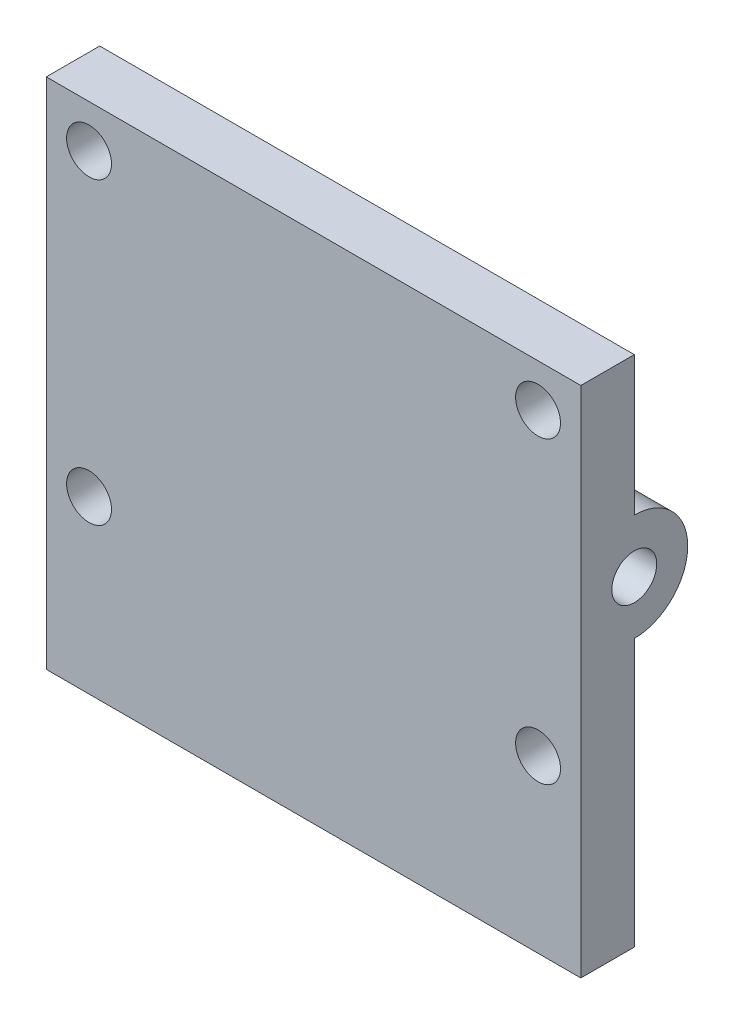
SolidWorks part; units mm, degrees
ref_plane "Płaszczyzna przednia" through (0, 0, 0) normal (0, 0, 1) x (1, 0, 0)
ref_plane "Płaszczyzna górna" through (0, 0, 0) normal (0, 1, 0) x (1, 0, 0)
ref_plane "Płaszczyzna prawa" through (0, 0, 0) normal (1, 0, 0) x (0, 0, -1)
sketch "Szkic2" plane through (0, 0, 0) normal (0, 0, 1) x (1, 0, 0)
  line L1 (-0.1189, 0.1751) -> (-0.1189, 24.1751)
  line L5 (24.8811, 24.1751) -> (24.8811, 0.1751)
  line L6 (-0.1189, 24.1751) -> (24.8811, 24.1751)
  line L17 (24.8811, 0.1751) -> (-0.1189, 0.1751)
  circle A0 centre (22.8811, 22.1751) radius 1.05
  circle A1 centre (22.8811, 8.1751) radius 1.05
  circle A2 centre (1.8811, 22.1751) radius 1.05
  circle A3 centre (1.8811, 8.1751) radius 1.05
  dimension "D1" = 2.1
  dimension "D2" = 2
  dimension "D3" = 2
  dimension "D4" = 14
  dimension "D5" = 21
  dimension "D7" = 25
  dimension "D8" = 24
extrude "Dodanie-wyciągnięcie1" add sketch "Szkic2" along normal blind 5
sketch "Szkic3" plane through (24.8811, 0, 0) normal (1, 0, 0) x (0, 0, -1)
  line L0 (0, 0.1751) -> (0, 24.1751) construction
  line L2 (-5, 24.1751) -> (0, 24.1751) construction
  circle A0 centre (-2.5, 15.1751) radius 1.05
  dimension "D1" = 2.1
  dimension "D3" = 9
  dimension "D2" = 2.5
extrude "Wytnij-wyciągnięcie1" cut sketch "Szkic3" against normal through all
sketch "Szkic4" plane through (-0.1189, 0, 0) normal (-1, 0, 0) x (0, 0, 1)
  line L0 (2.5, 24.1751) -> (2.5, 17.6751)
  line L1 (5, 24.1751) -> (0, 24.1751) construction
  line L2 (2.5, 17.6751) -> (0, 17.6751)
  line L4 (0, 24.1751) -> (0, 0.1751) construction
  line L5 (0, 12.6751) -> (2.5, 12.6751)
  line L6 (2.5, 12.6751) -> (2.5, 0.1751)
  line L7 (5, 0.1751) -> (0, 0.1751) construction
  line L8 (2.5, 24.1751) -> (0, 24.1751)
  line L9 (0, 24.1751) -> (0, 17.6751)
  line L10 (0, 12.6751) -> (0, 0.1751)
  line L11 (0, 0.1751) -> (2.5, 0.1751)
  dimension "D1" = 6.5
  dimension "D2" = 12.5
  dimension "D3" = 2.5
  dimension "D4" = 2.5
extrude "Wytnij-wyciągnięcie2" cut sketch "Szkic4" against normal through all
fillet "Zaokrąglenie5" radius 2.5 2 edges at (12.3811, 12.6751, 0) (12.3811, 17.6751, 0)
